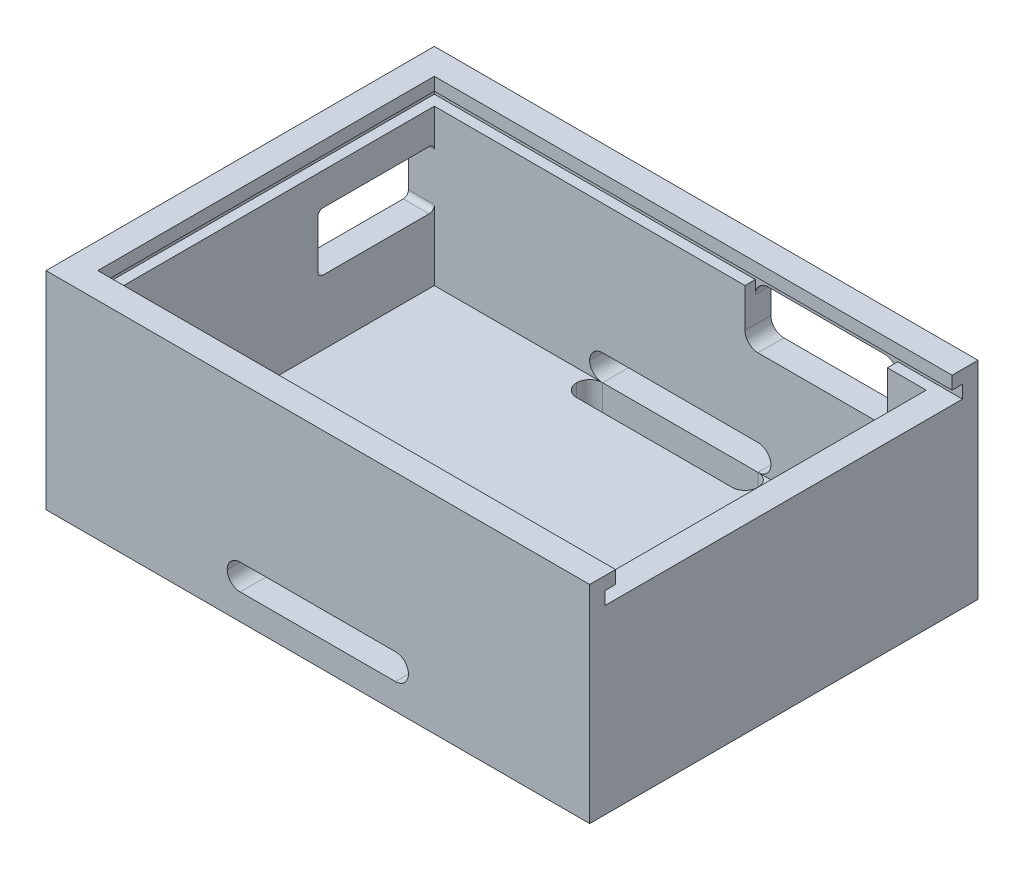
SolidWorks part; units mm, degrees
ref_plane "前视基准面" through (0, 0, 0) normal (0, 0, 1) x (1, 0, 0)
ref_plane "上视基准面" through (0, 0, 0) normal (0, 1, 0) x (1, 0, 0)
ref_plane "右视基准面" through (0, 0, 0) normal (1, 0, 0) x (0, 0, -1)
sketch "草图1" plane through (0, 0, 0) normal (0, 1, 0) x (1, 0, 0)
  line L1 (-21, 15) -> (21, 15)
  line L2 (-21, 15) -> (-21, -15)
  line L3 (-21, -15) -> (21, -15)
  line L4 (21, 15) -> (21, -15)
  line L5 (-21, 15) -> (21, -15) construction
  line L6 (-21, -15) -> (21, 15) construction
  point P0 (0, 0)
  dimension "D1" = 42
  dimension "D2" = 30
extrude "凸台-拉伸1" add sketch "草图1" along normal blind 16
shell "抽壳1" thickness 2 removed face at (0, 16, 0)
sketch "草图2" plane through (21, 0, 0) normal (1, 0, 0) x (0, 0, -1)
  line L0 (-15, 16) -> (15, 16) construction
  line L1 (-6, 16) -> (6, 16)
  line L2 (-6, 16) -> (-6, 9)
  line L3 (-6, 9) -> (6, 9)
  line L4 (6, 16) -> (6, 9)
  point P6 (0, 16)
  dimension "D1" = 7
  dimension "D2" = 12
extrude "切除-拉伸1" [suppressed] cut sketch "草图2" against normal up to next
sketch "草图3" plane through (-19, 0, 0) normal (1, 0, 0) x (0, 0, -1)
  line L0 (13, 2) -> (-13, 2) construction
  line L1 (-5, 15) -> (5, 15)
  line L2 (-5, 15) -> (-5, 11)
  line L3 (-5, 11) -> (5, 11)
  line L4 (5, 15) -> (5, 11)
  point P6 (0, 15)
  dimension "D1" = 9
  dimension "D2" = 10
  dimension "D3" = 4
extrude "切除-拉伸2" [suppressed] cut sketch "草图3" against normal up to next
fillet "圆角1" [suppressed] radius 1
fillet "圆角2" [suppressed] radius 2
sketch "草图4" plane through (21, 0, 0) normal (1, 0, 0) x (0, 0, -1)
  line L0 (-15, 16) -> (15, 16) construction
  line L1 (-13, 16) -> (13, 16)
  line L2 (-13, 16) -> (-13, 14)
  line L3 (-13, 14) -> (13, 14)
  line L4 (13, 16) -> (13, 14)
  line L5 (-13, 16) -> (-13, 2) construction
  line L6 (13, 16) -> (13, 2) construction
  dimension "D1" = 2
extrude "切除-拉伸3" cut sketch "草图4" against normal up to next
sketch "草图5" plane through (21, 0, 0) normal (1, 0, 0) x (0, 0, -1)
  line L0 (-15, 16) -> (-15, 0) construction
  line L1 (-13.8, 15) -> (13.8, 15)
  line L2 (-13.8, 15) -> (-13.8, 14)
  line L3 (-13.8, 14) -> (13.8, 14)
  line L4 (13.8, 15) -> (13.8, 14)
  line L5 (15, 16) -> (15, 0) construction
  line L6 (-15, 16) -> (-13, 16) construction
  dimension "D1" = 1.2
  dimension "D2" = 1.2
  dimension "D3" = 1
  dimension "D4" = 1
extrude "切除-拉伸4" cut sketch "草图5" against normal offset from surface (40.8 mm away) 0.8 up to face at (-19, 9, 0) offset beyond the face yes
sketch "草图6" plane through (-21, 0, 0) normal (-1, 0, 0) x (0, 0, 1)
  line L0 (-15, 16) -> (-15, 0) construction
  line L1 (15, 16) -> (15, 0) construction
  line L3 (13.8, 14) -> (13.8, 15) construction
  circle A0 centre (-9, 14.5) radius 0.8
  circle A1 centre (9, 14.5) radius 0.8
  point P10 (13.8, 14.5)
  dimension "D1" = 1.6
  dimension "D2" = 6
  dimension "D3" = 6
extrude "切除-拉伸5" [suppressed] cut sketch "草图6" against normal up to next
sketch "草图8" plane through (0, 0, 0) normal (0, -1, 0) x (1, 0, 0)
  line L0 (21, -15) -> (-21, -15) construction
  line L1 (-7, -11) -> (7, -11)
  line L2 (-7, -11) -> (-7, -13)
  line L3 (-7, -13) -> (7, -13)
  line L4 (7, -11) -> (7, -13)
  point P6 (0, -11)
  dimension "D1" = 14
  dimension "D2" = 2
  dimension "D3" = 2
extrude "切除-拉伸6" cut sketch "草图8" against normal up to next
sketch "草图9" plane through (0, 0, -15) normal (0, 0, -1) x (-1, 0, 0)
  line L0 (-21, 0) -> (21, 0) construction
  line L1 (-7, 4) -> (7, 4)
  line L2 (-7, 4) -> (-7, 2)
  line L3 (-7, 2) -> (7, 2)
  line L4 (7, 4) -> (7, 2)
  point P6 (0, 4)
  dimension "D1" = 14
  dimension "D2" = 2
  dimension "D3" = 2
extrude "切除-拉伸7" cut sketch "草图9" against normal up to next
fillet "圆角3" radius 1 4 edges at (-7, 4, -14) (-7, 2, -14) (7, 2, -14) (7, 4, -14)
fillet "圆角4" radius 1 4 edges at (-7, 1, -13) (-7, 1, -11) (7, 1, -13) (7, 1, -11)
mirror "镜向1" about plane through (0, 0, 0) normal (0, 0, 1) of "圆角4", "圆角3", "切除-拉伸6", "切除-拉伸7"
sketch "草图10" plane through (-21, 0, 0) normal (-1, 0, 0) x (0, 0, 1)
  line L0 (-13, 2) -> (-13, 3) construction
  line L1 (-13, 11.5) -> (-4, 11.5)
  line L2 (-13, 11.5) -> (-13, 7)
  line L3 (-13, 7) -> (-4, 7)
  line L4 (-4, 11.5) -> (-4, 7)
  line L5 (-13, 2) -> (13, 2) construction
  dimension "D1" = 9
  dimension "D2" = 5
  dimension "D3" = 4.5
extrude "切除-拉伸8" cut sketch "草图10" against normal up to next
sketch "草图11" plane through (0, 0, -15) normal (0, 0, -1) x (-1, 0, 0)
  line L0 (-19, 2) -> (-6, 2) construction
  line L1 (-16, 14) -> (-5, 14)
  line L2 (-16, 14) -> (-16, 10)
  line L3 (-16, 10) -> (-5, 10)
  line L4 (-5, 14) -> (-5, 10)
  line L5 (-19, 14) -> (-19, 2) construction
  line L6 (19, 14) -> (-19, 14) construction
  dimension "D1" = 8
  dimension "D2" = 11
  dimension "D3" = 3
extrude "切除-拉伸9" cut sketch "草图11" against normal up to next
fillet "圆角5" radius 1 4 edges at (5, 14, -14.4) (5, 10, -14) (16, 10, -14) (16, 14, -14.4)
fillet "圆角6" radius 0.4 4 edges at (-20, 11.5, -13) (-20, 11.5, -4) (-20, 7, -4) (-20, 7, -13)
